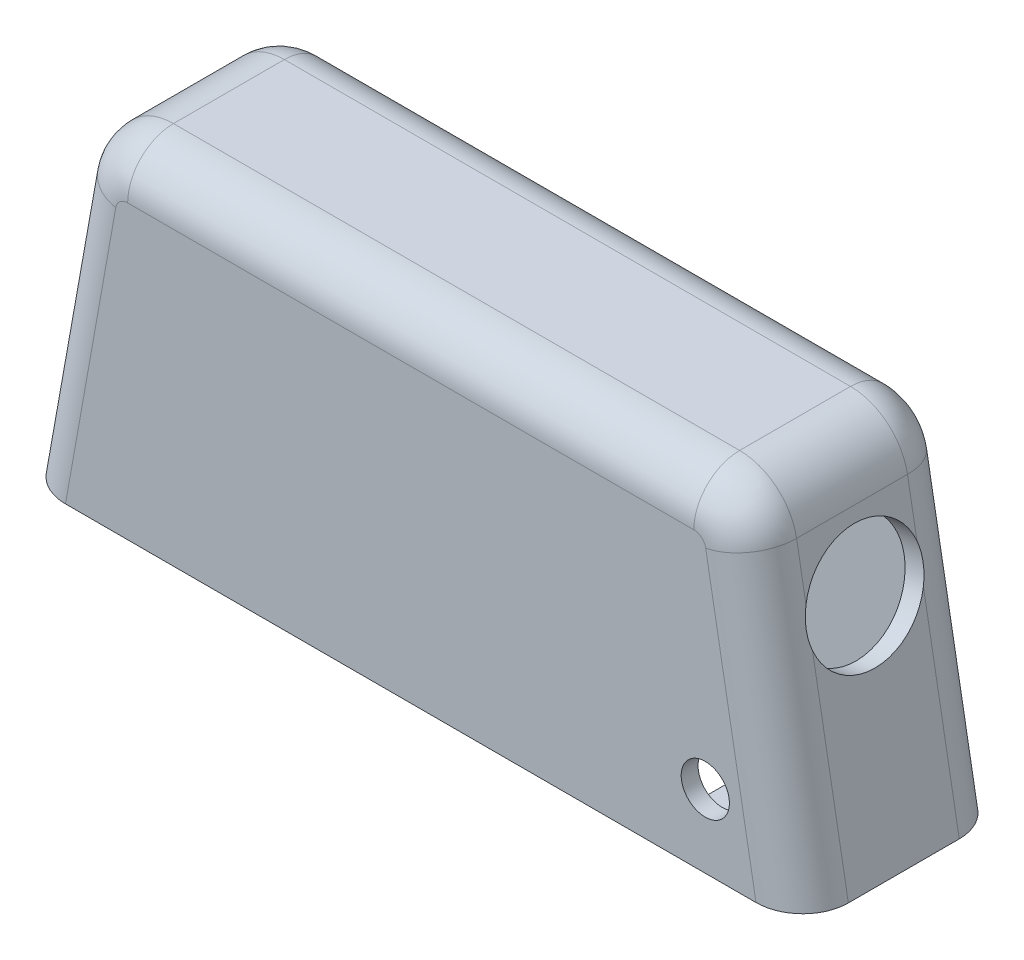
SolidWorks part; units mm, degrees
ref_plane "Front Plane" through (0, 0, 0) normal (0, 0, 1) x (1, 0, 0)
ref_plane "Top Plane" through (0, 0, 0) normal (0, 1, 0) x (1, 0, 0)
ref_plane "Right Plane" through (0, 0, 0) normal (1, 0, 0) x (0, 0, -1)
sketch "Sketch1" plane through (0, 0, 0) normal (0, 0, 1) x (1, 0, 0)
  line L1 (0, 0) -> (65, 0)
  line L3 (5, 28) -> (60, 28)
  line L6 (5, 28) -> (0, 0)
  line L7 (0, 0) -> (1.0896, 0.681)
  line L8 (60, 28) -> (65, 0)
  line L9 (65, 0) -> (64.8327, 0.1362)
  dimension "D1" = 65
extrude "Boss-Extrude1" add sketch "Sketch1" along normal blind 1.8 contours L8 L3 L6 L1 region at (32.5, 13.6111, 0)
sketch "Sketch2" plane through (0, 0, 1.8) normal (0, 0, 1) x (1, 0, 0)
  line L0 (5, 28) -> (60, 28)
  line L1 (60, 28) -> (65, 0)
  line L2 (65, 0) -> (0, 0)
  line L3 (0, 0) -> (5, 28)
  line L4 (6.5182, 26.4) -> (58.6604, 26.4)
  line L5 (58.6604, 26.4) -> (63.089, 1.6)
  line L6 (63.089, 1.6) -> (2.0896, 1.6)
  line L7 (6.5182, 26.4) -> (2.0896, 1.6)
  dimension "D1" = 1.6
  dimension "D2" = 1.6
  dimension "D3" = 1.6
extrude "Boss-Extrude2" add sketch "Sketch2" along normal blind 15
sketch "Sketch3" plane through (62.9913, 11.2485, 0) normal (0.9844, 0.1758, 0) x (0, 0, -1)
  line L0 (-8.4, 17.0165) -> (-8.4, -11.4264) construction
  line L1 (-16.8, 17.0165) -> (0, 17.0165) construction
  line L2 (-16.8, -11.4264) -> (0, -11.4264) construction
  circle A0 centre (-8.4, 7.0165) radius 4.85
  dimension "D1" = 9.7
  dimension "D2" = 10
extrude "Cut-Extrude1" cut sketch "Sketch3" against normal blind 15
sketch "Sketch4" plane through (0, 0, 0) normal (-0.9844, 0.1758, 0) x (0, 0, 1)
  line L0 (8.4, 28.4429) -> (8.4, 0) construction
  line L1 (16.8, 28.4429) -> (0, 28.4429) construction
  line L2 (16.8, 0) -> (0, 0) construction
  circle A0 centre (8.4, 18.4429) radius 4.85
  dimension "D1" = 9.7
  dimension "D2" = 10
extrude "Cut-Extrude2" cut sketch "Sketch4" against normal blind 15
fillet "Fillet1" radius 3 2 edges at (6.5182, 26.4, 9.3) (58.6604, 26.4, 9.3)
fillet "Fillet2" radius 4.8 2 edges at (60, 28, 8.4) (5, 28, 8.4)
fillet "Fillet3" radius 2 5 edges at (61.0955, 12.7637, 1.8) (58.0745, 25.7002, 1.8) (4.0831, 12.7637, 1.8) (7.1041, 25.7002, 1.8) (32.5893, 26.4, 1.8)
fillet "Fillet4" radius 3.8 5 edges at (2.1468, 12.0219, 0) (5.9374, 26.8804, 0) (62.8532, 12.0219, 0) (59.0626, 26.8804, 0) (32.5, 28, 0)
sketch "Sketch5" plane through (0, 0, 16.8) normal (0, 0, 1) x (1, 0, 0)
  line L1 (2.0896, 1.6) -> (62.8532, 1.6)
  line L3 (3.2013, 12.0219) -> (62.1718, 12.0219)
  line L5 (3.2013, 12.0219) -> (1.2737, 1.6)
  line L6 (1.2737, 1.6) -> (2.0896, 1.6)
  line L7 (62.1718, 12.0219) -> (63.8663, 1.6)
  line L8 (63.8663, 1.6) -> (62.8532, 1.6)
extrude "Boss-Extrude3" add sketch "Sketch5" against normal blind 1.4
sketch "Sketch6" plane through (0, 0, 16.8) normal (0, 0, 1) x (1, 0, 0)
  circle A0 centre (56.9334, 6.0339) radius 2
  dimension "D1" = 4
extrude "Cut-Extrude3" cut sketch "Sketch6" against normal blind 1.4
sketch "Sketch7" plane through (0, 0, 16.8) normal (0, 0, 1) x (1, 0, 0)
  line L0 (6.1555, 26.7116) -> (3.9507, 17.3334)
  line L1 (3.9507, 12.0219) -> (61.5079, 12.0219)
  line L2 (3.9507, 12.0219) -> (3.9507, 17.3334)
  line L4 (61.5079, 12.0219) -> (61.5079, 17.3334)
  line L5 (58.9319, 26.7116) -> (61.5079, 17.3334)
  line L11 (6.1555, 26.7116) -> (58.9319, 26.7116)
extrude "Boss-Extrude4" add sketch "Sketch7" against normal blind 1.4
sketch "Sketch8" plane through (0, 0, 0) normal (0, -1, 0) x (-1, 0, 0)
  line L0 (-3.8601, 0) -> (-61.1399, 0) construction
  line L1 (-53, -1.8) -> (-12, -1.8)
  line L2 (-53, -1.8) -> (-53, -15.4)
  line L3 (-53, -15.4) -> (-12, -15.4)
  line L4 (-12, -1.8) -> (-12, -15.4)
  line L5 (0, -16.8) -> (-65, -16.8) construction
  line L6 (-65, -16.8) -> (-65, -3.8) construction
  line L7 (0, -16.8) -> (0, -3.8) construction
  dimension "D1" = 1.8
  dimension "D2" = 1.4
  dimension "D3" = 12
  dimension "D4" = 12
extrude "Cut-Extrude4" cut sketch "Sketch8" against normal blind 4.4
fillet "Fillet5" radius 1.8 5 edges at (4.0831, 12.7637, 15.4) (7.1041, 25.7002, 15.4) (61.0955, 12.7637, 15.4) (58.0745, 25.7002, 15.4) (32.5893, 26.4, 15.4)
fillet "Fillet6" radius 3.8 5 edges at (62.8532, 12.0219, 16.8) (59.0626, 26.8804, 16.8) (32.5, 28, 16.8) (5.9374, 26.8804, 16.8) (2.1468, 12.0219, 16.8)
